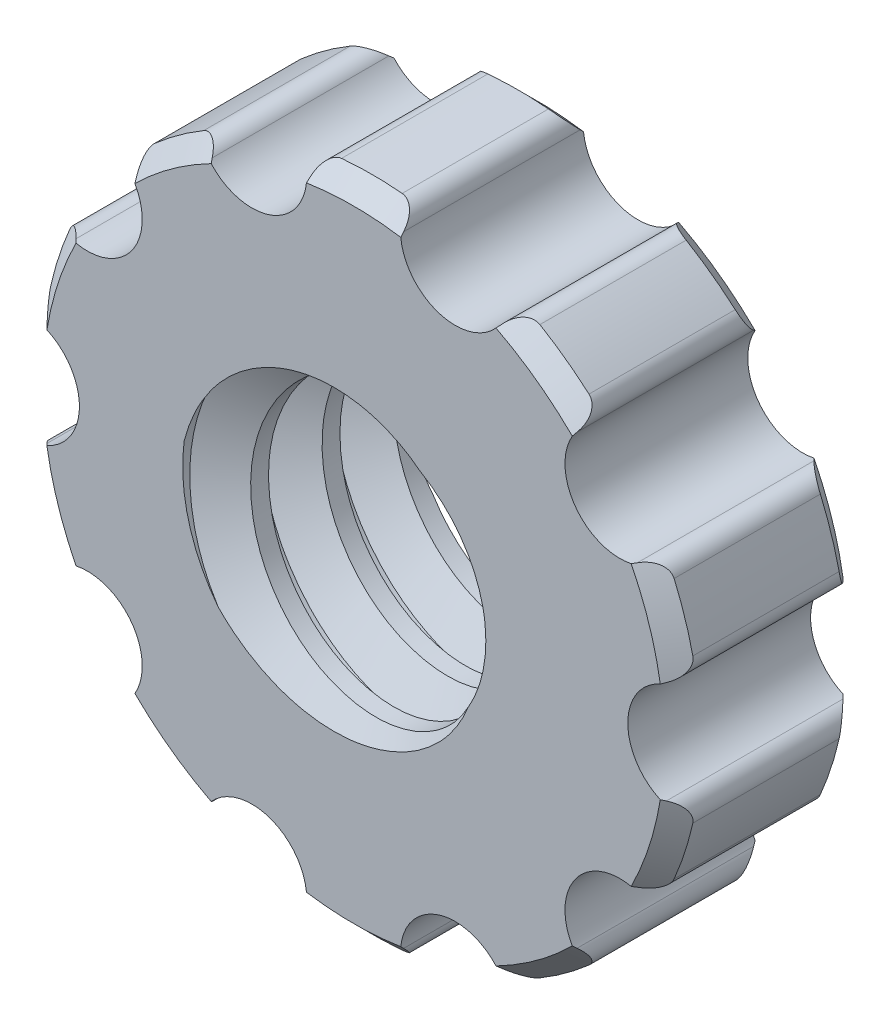
SolidWorks part; units mm, degrees
material "Custom Plastic"
ref_plane "Front" through (0, 0, 0) normal (0, 0, 1) x (1, 0, 0)
ref_plane "Top" through (0, 0, 0) normal (0, 1, 0) x (1, 0, 0)
ref_plane "Right" through (0, 0, 0) normal (1, 0, 0) x (0, 0, -1)
sketch "Sketch1" plane through (0, 0, 0) normal (0, 0, 1) x (1, 0, 0)
  circle A0 centre (0, 0) radius 9
  circle A1 centre (0, 0) radius 4.675
  dimension "D1" = 9.35
  dimension "D2" = 18
extrude "Boss-Extrude1" add sketch "Sketch1" along normal blind 5
thread "Thread1" pitch 1.9538 method extrude profile "Thread Profile1" start angle 0, offset 1.75, length 0, pitch 1.9538, diameter 9.35
ref_plane "Plane1" through (-4.675, 0, 6.75) normal (0, -1, 0) x (-1, 0, 0)
sketch "Thread Profile1" plane through (-4.675, 0, 6.75) normal (0, -1, 0) x (-1, 0, 0)
  line L0 (0, 0) -> (0, 1.9538) construction
  line L11 (0, 0) -> (0, 1.7096)
  line L12 (0, 1.7096) -> (-1.0576, 1.099)
  line L13 (-1.0576, 1.099) -> (-1.0576, 0.6106)
  line L15 (-1.0576, 0.6106) -> (0, 0)
  line L17 (-1.0576, 0.8548) -> (0, 0.8548) construction
  point P2 (0, 0)
  dimension "Pitch" = 1.9538
  dimension "Profile_Angle" = 60
  dimension "Profile_Land" = 0.4885
  dimension "Profile_Height" = 1.0576
sketch "Sketch4" plane through (0, 0, 0) normal (0, 0, -1) x (-1, 0, 0)
  circle A0 centre (0, 0) radius 9.4647
extrude "Cut-Extrude1" cut sketch "Sketch4" along normal blind 6
sketch "Sketch5" plane through (0, 0, 5) normal (0, 0, 1) x (1, 0, 0)
  circle A0 centre (0, 0) radius 9.4647
extrude "Cut-Extrude2" cut sketch "Sketch5" along normal blind 6
chamfer "Chamfer1" distance 0.5 angle 45 2 edges at (9, 0, 5) (9, 0, 0)
sketch "Sketch6" plane through (0, 0, 5) normal (0, 0, 1) x (1, 0, 0)
  circle A0 centre (-9, 0) radius 1.5
  circle A1 centre (0, 0) radius 9 construction
  dimension "D1" = 3
extrude "Cut-Extrude3" cut sketch "Sketch6" against normal through all
fillet "Fillet1" radius 0.5 2 edges at (-8.875, -1.4948, 2.5) (-8.875, 1.4948, 2.5)
pattern_circular "CirPattern1" count 10 over 360 about axis through (0, 0, 5) along (0, 0, -1) of "Cut-Extrude3", "Fillet1"
